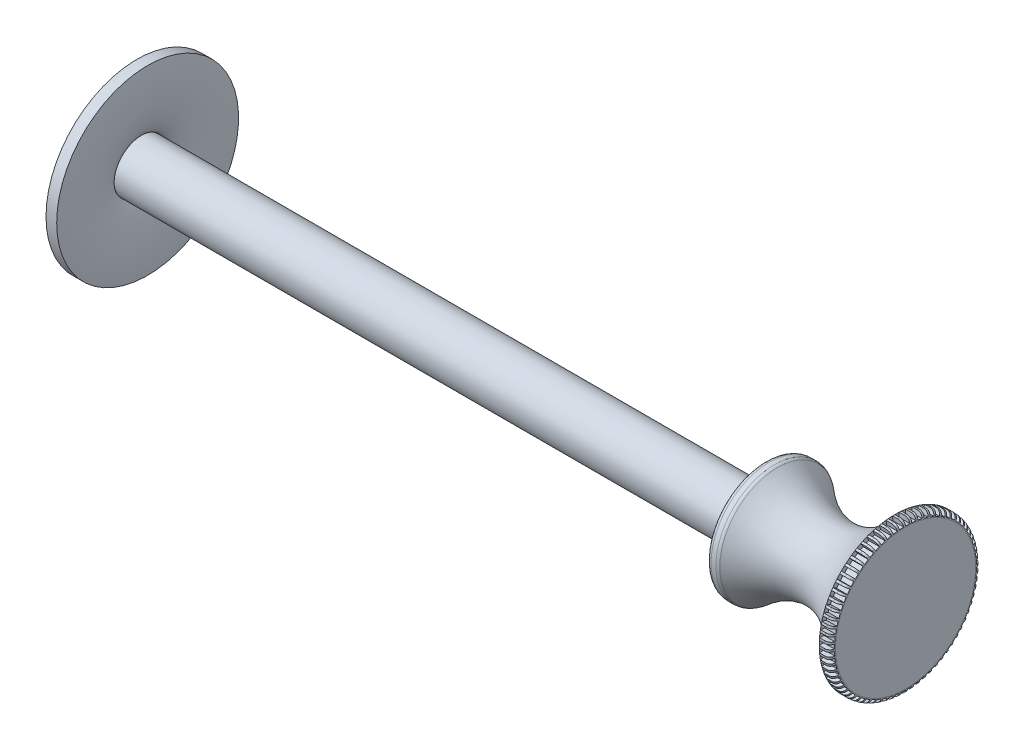
SolidWorks part; units mm, degrees
ref_plane "Přední rovina" through (0, 0, 0) normal (0, 0, 1) x (1, 0, 0)
ref_plane "Horní rovina" through (0, 0, 0) normal (0, 1, 0) x (1, 0, 0)
ref_plane "Pravá rovina" through (0, 0, 0) normal (1, 0, 0) x (0, 0, -1)
sketch "Skica1" plane through (0, 0, 0) normal (0, 1, 0) x (1, 0, 0)
  line L0 (0, 0) -> (-13, 0)
  line L1 (0, 0) -> (45, 0)
  line L2 (-14, 0.0749) -> (-14, -2.4251)
  line L3 (-14, -2.4251) -> (25.1376, -2.4251)
  line L4 (-13.2111, 6) -> (-12.2206, 6)
  line L5 (45, 0) -> (45, 3)
  line L6 (45, 3) -> (46, 3)
  line L8 (25.1376, -2.4251) -> (58, -2.4251)
  line L10 (57, 4.5749) -> (58, 4.5749)
  line L11 (58, 4.5749) -> (58, -2.4251)
  ellipse E0 centre (-14, 4.0749) end of major axis (-14, 0.0749) minor radius 0.9 (-14, 0.0749) -> (-13.2111, 6) ccw
  ellipse E1 centre (-13, 4) end of major axis (-13, 0) minor radius 0.9 (-13, 0) -> (-12.2206, 6) ccw
  spline S0 degree 2 poles (46, 3) (51.8561, -2.3062) (57, 4.5749) knots 0 0 0 1 1 1
  dimension "D2" = 45
  dimension "D3" = 2.5
  dimension "D4" = 3
  dimension "D5" = 1
  dimension "D6" = 7
  dimension "D7" = 4
  dimension "D8" = 1
  dimension "D9" = 6
  dimension "D10" = 11
  dimension "D11" = 13
  dimension "D12" = 1
  dimension "D13" = 59
revolve "Rotovat1" add sketch "Skica1" angle 360 about L3
fillet "Zaoblit2" radius 0.5 1 edges at (58, 0, 9.4251)
fillet "Zaoblit3" radius 0.4 2 edges at (45, 0, 7.8502) (46, 0, 7.8502)
ref_plane "Rovina1" through (0, 0, 9.5) normal (0, 0, 1) x (1, 0, 0)
sketch "Skica2" plane through (0, 0, 9.5) normal (0, 0, 1) x (1, 0, 0)
  line L0 (57, 0) -> (57, 0.4)
  line L1 (57, 0) -> (59, 0)
  line L2 (59, 0) -> (59, 0.4)
  line L3 (57, 0.4) -> (59, 0.4)
  line L4 (58, 0) -> (72.8698, 0) construction
  line L5 (58, -6.5) -> (58, 6.5) construction
  dimension "D1" = 2
  dimension "D2" = 0.4
extrude "Odebrat vysunutím1" cut sketch "Skica2" against normal blind 0.5
ref_axis "Osa1" through (45, 0, 2.4251) along (-1, 0, 0)
pattern_circular "Kruhové pole1" count 72 every 5 about axis through (45, 0, 2.4251) along (-1, 0, 0) of "Odebrat vysunutím1"
